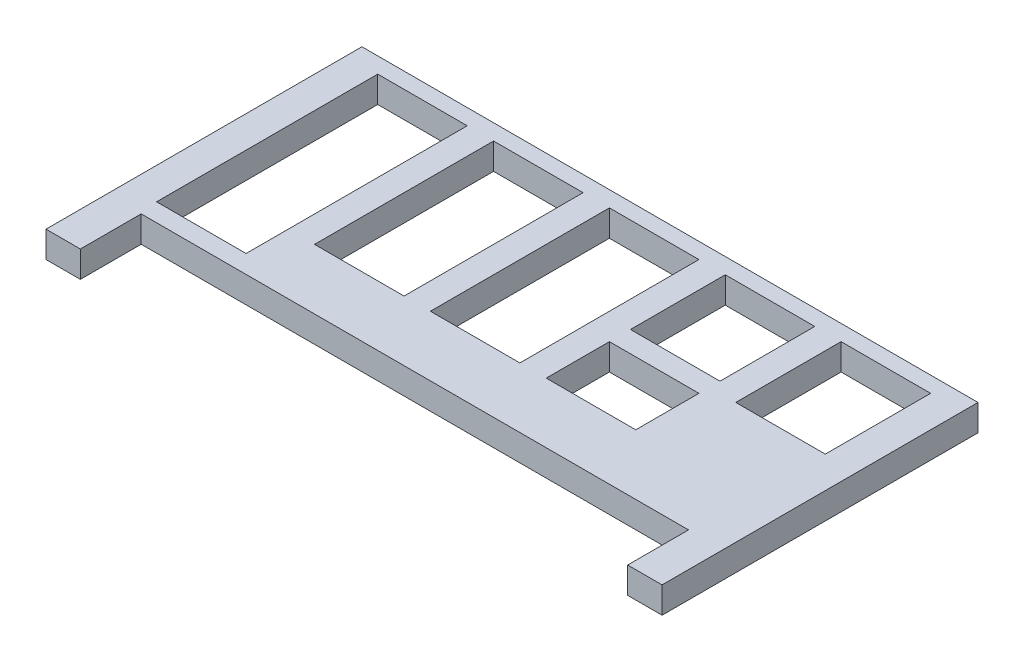
SolidWorks part; units mm, degrees
ref_plane "Front" through (0, 0, 0) normal (0, 0, 1) x (1, 0, 0)
ref_plane "Top" through (0, 0, 0) normal (0, 1, 0) x (1, 0, 0)
ref_plane "Right" through (0, 0, 0) normal (1, 0, 0) x (0, 0, -1)
sketch "Sketch1" plane through (0, 0, 0) normal (0, 1, 0) x (1, 0, 0)
  line L1 (-58.5, -30) -> (58.5, -30)
  line L2 (-58.5, -30) -> (-58.5, 30)
  line L3 (-58.5, 30) -> (58.5, 30)
  line L4 (58.5, -30) -> (58.5, 30)
  line L5 (-58.5, -30) -> (58.5, 30) construction
  line L6 (-58.5, 30) -> (58.5, -30) construction
  line L12 (13.5, 9) -> (30.5, 9)
  line L13 (-52.5, -15) -> (-35.5, -15)
  line L14 (-52.5, -15) -> (-52.5, 27)
  line L15 (-52.5, 27) -> (-35.5, 27)
  line L16 (-35.5, -15) -> (-35.5, 27)
  line L17 (-52.5, -15) -> (-35.5, 27) construction
  line L18 (-52.5, 27) -> (-35.5, -15) construction
  line L23 (13.5, 9) -> (13.5, 27)
  line L24 (13.5, 27) -> (30.5, 27)
  line L25 (-13.5, 27) -> (-30.5, 27)
  line L26 (-13.5, 27) -> (-13.5, -7)
  line L27 (-13.5, -7) -> (-30.5, -7)
  line L28 (-30.5, 27) -> (-30.5, -7)
  line L29 (-13.5, 27) -> (-30.5, -7) construction
  line L30 (-13.5, -7) -> (-30.5, 27) construction
  line L35 (30.5, 9) -> (30.5, 27)
  line L36 (13.5, 9) -> (30.5, 27) construction
  line L37 (-8.5, -7) -> (8.5, -7)
  line L38 (-8.5, -7) -> (-8.5, 27)
  line L39 (-8.5, 27) -> (8.5, 27)
  line L40 (8.5, -7) -> (8.5, 27)
  line L41 (-8.5, -7) -> (8.5, 27) construction
  line L42 (-8.5, 27) -> (8.5, -7) construction
  line L48 (13.5, 27) -> (30.5, 9) construction
  line L49 (35.5, 7) -> (52.5, 7)
  line L50 (35.5, 7) -> (35.5, 27)
  line L51 (35.5, 27) -> (52.5, 27)
  line L52 (52.5, 7) -> (52.5, 27)
  line L53 (35.5, 7) -> (52.5, 27) construction
  line L54 (35.5, 27) -> (52.5, 7) construction
  line L55 (13.5, 5) -> (30.5, 5)
  line L56 (13.5, 5) -> (13.5, -7)
  line L57 (13.5, -7) -> (30.5, -7)
  line L58 (30.5, 5) -> (30.5, -7)
  line L59 (13.5, 5) -> (30.5, -7) construction
  line L60 (13.5, -7) -> (30.5, 5) construction
  line L61 (51.975, -30) -> (58.5, -30)
  line L67 (-51.975, -30) -> (51.975, -30)
  line L68 (-51.975, -30) -> (-51.975, -18.45)
  line L69 (-51.975, -18.45) -> (51.975, -18.45)
  line L70 (51.975, -30) -> (51.975, -18.45)
  point P0 (0, 0)
  point P6 (44, 17)
  point P9 (22, 18)
  point P11 (-44, 6)
  point P21 (-22, 10)
  point P26 (22, -1)
  point P31 (0, 10)
  dimension "D1" = 117
  dimension "D2" = 60
  dimension "D3" = 6
  dimension "D4" = 3
  dimension "D5" = 17
  dimension "D6" = 5
  dimension "D7" = 17
  dimension "D8" = 3
  dimension "D9" = 5
  dimension "D10" = 3
  dimension "D11" = 17
  dimension "D12" = 5
  dimension "D13" = 17
  dimension "D14" = 18
  dimension "D15" = 5
  dimension "D16" = 17
  dimension "D17" = 20
  dimension "D18" = 12
  dimension "D19" = 6
  dimension "D20" = 6.525
  dimension "D21" = 42
  dimension "D22" = 34
  dimension "D23" = 4
  dimension "D25" = 34
  dimension "D26" = 11.55
  dimension "D27" = 103.95
extrude "Boss-Extrude1" add sketch "Sketch1" along normal blind 5 contours L68 L69 L1 L4 L3 L2 L52 L49 L50 L51 L40 L37 L38 L39 L35 L12 L23 L24 L28 L25 L26 L27 L16 L13 L14 L15 L55 L58 L57 L56 region at (-57.1851, 0, 0)
